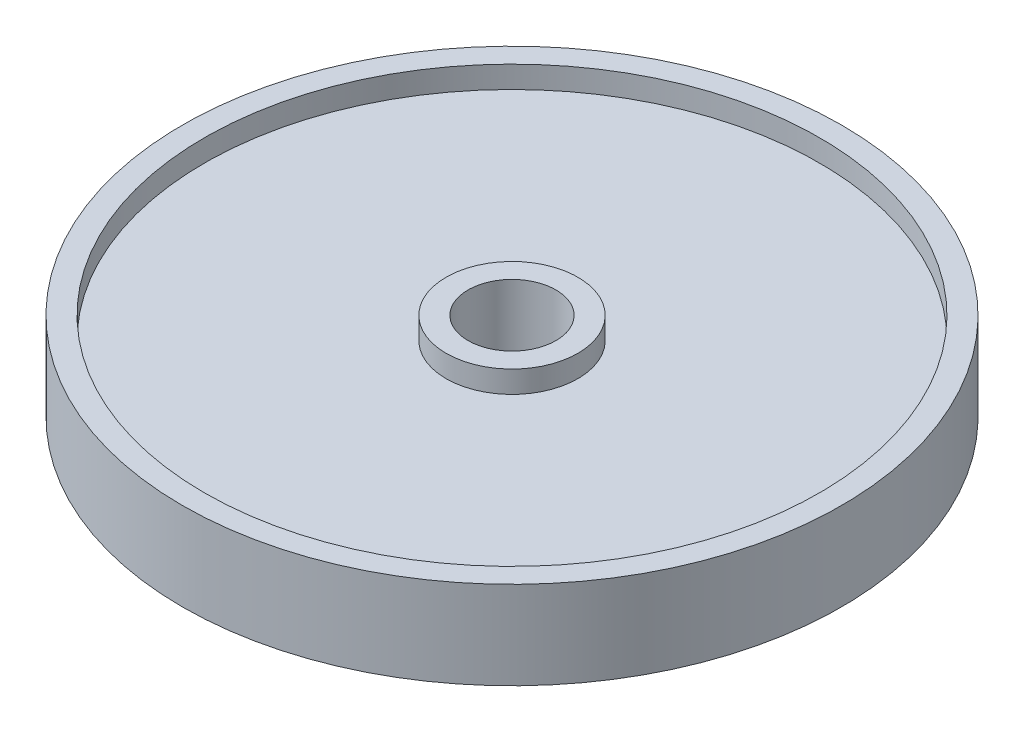
SolidWorks part; units mm, degrees
ref_plane "Front Plane" through (0, 0, 0) normal (0, 0, 1) x (1, 0, 0)
ref_plane "Top Plane" through (0, 0, 0) normal (0, 1, 0) x (1, 0, 0)
ref_plane "Right Plane" through (0, 0, 0) normal (1, 0, 0) x (0, 0, -1)
sketch "Sketch1" plane through (0, 0, 0) normal (0, 1, 0) x (1, 0, 0)
  circle A0 centre (0, 0) radius 35
  circle A1 centre (0, 0) radius 37.5
  circle A2 centre (0, 0) radius 5
  circle A3 centre (0, 0) radius 7.5
  dimension "D1" = 15
  dimension "D2" = 10
  dimension "D3" = 70
  dimension "D4" = 75
extrude "Boss-Extrude1" add sketch "Sketch1" along normal mid plane 5 contours A0 A3 region at (-34.0101, 0, 0)
extrude "Boss-Extrude2" add sketch "Sketch1<3>" along normal mid plane 10 contours A1 A0 | A3 A2 region at (-36.4393, 0, 0) region at (-7.2879, 0, 0)
sketch "Sketch1<3>" plane through (0, 0, 0) normal (0, 1, 0) x (1, 0, 0) same geometry as "Sketch1"
